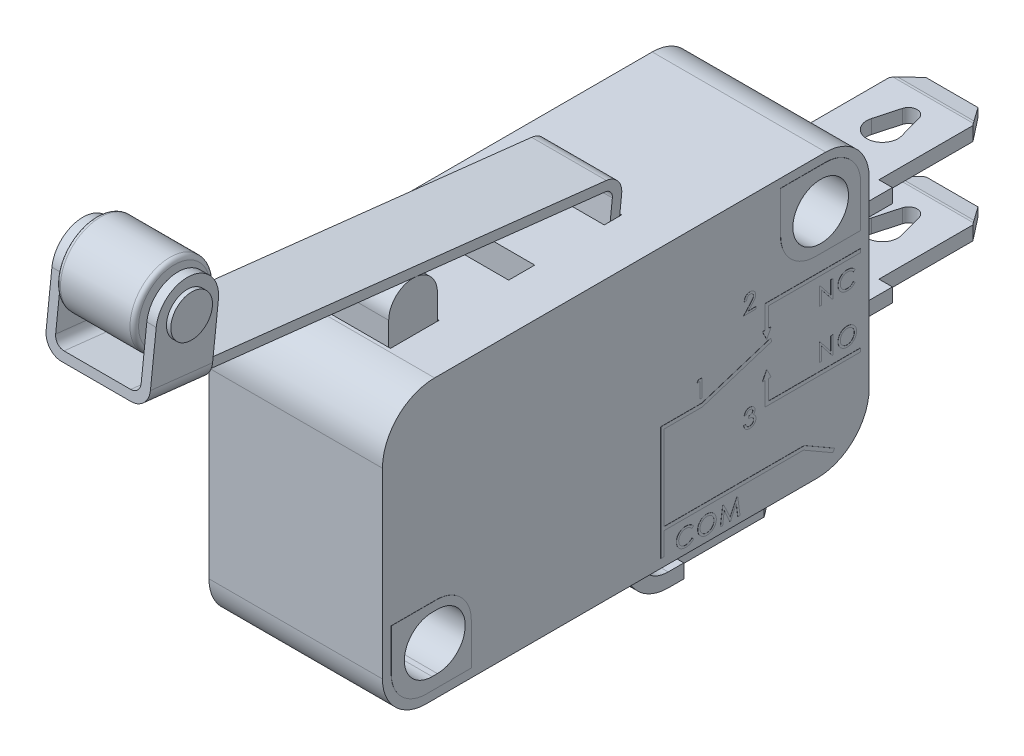
SolidWorks part; units mm, degrees
other "Switch Body"
other "Connections"
other "Lever with Wheel"
material "ABS"
ref_plane "Front Plane" through (0, 0, 0) normal (0, 0, 1) x (1, 0, 0)
ref_plane "Top Plane" through (0, 0, 0) normal (0, 1, 0) x (1, 0, 0)
ref_plane "Right Plane" through (0, 0, 0) normal (1, 0, 0) x (0, 0, -1)
sketch "Sketch1" plane through (0, 0, 0) normal (1, 0, 0) x (0, 0, -1)
  line L0 (-14, 0) -> (0, 0) construction
  line L1 (-11, 8) -> (11.5, 8)
  line L2 (-14, 5) -> (-14, -5.5)
  line L3 (-11.5, -8) -> (11, -8)
  line L4 (14, 5.5) -> (14, -5)
  line L5 (0, 0) -> (14, 0) construction
  line L6 (0, 0) -> (0, -8) construction
  line L7 (0, 0) -> (0, 8) construction
  arc A0 (-11, 8) -> (-14, 5) centre (-11, 5) ccw
  arc A1 (11, -8) -> (14, -5) centre (11, -5) ccw
  arc A2 (-14, -5.5) -> (-11.5, -8) centre (-11.5, -5.5) ccw
  arc A3 (11.5, 8) -> (14, 5.5) centre (11.5, 5.5) cw
  dimension "D3" = 3
  dimension "D4" = 2.5
  dimension "D1" = 28
  dimension "D2" = 16
extrude "Body Extrude" add sketch "Sketch1" along normal mid plane 9.98
sketch "Sketch4" plane through (4.99, 0, 0) normal (1, 0, 0) x (0, 0, -1)
  line L0 (-11.15, -5.2) -> (-10.85, -5.2) construction
  line L1 (-11.15, -3.6) -> (-10.85, -3.6)
  line L2 (-11.15, -6.8) -> (-10.85, -6.8)
  line L3 (-11.15, -5.2) -> (-12.75, -5.2) construction
  line L4 (-10.85, -5.2) -> (-9.25, -5.2) construction
  line L5 (11.2, 5.2) -> (11.2, 6.8) construction
  line L6 (11.2, 6.8) -> (11.2, 8) construction
  line L7 (11.5, 8) -> (-11, 8) construction
  line L8 (11.2, 5.2) -> (12.8, 5.2) construction
  line L9 (12.8, 5.2) -> (14, 5.2) construction
  line L10 (14, -5) -> (14, 5.5) construction
  line L11 (11.2, 5.2) -> (11.2, 3.6) construction
  line L13 (-11.5, -8) -> (11, -8) construction
  line L15 (-14, 5) -> (-14, -5.5) construction
  circle A0 centre (11.2, 5.2) radius 1.6
  arc A1 (-11.15, -3.6) -> (-11.15, -6.8) centre (-11.15, -5.2) ccw
  arc A2 (-10.85, -6.8) -> (-10.85, -3.6) centre (-10.85, -5.2) ccw
  point P4 (-11, -5.2)
  dimension "D1" = 3.2
  dimension "D2" = 3.2
  dimension "D3" = 3.5
  dimension "D4" = 1.2
  dimension "D5" = 1.2
  dimension "D6" = 2.8
  dimension "D7" = 2.8
  dimension "D8" = 11.6
  dimension "D9" = 1.2
  dimension "D10" = 3
  dimension "D11" = 2.8
  dimension "D12" = 11.6
extrude "Mount Holes Cut" cut sketch "Sketch4" against normal up to surface (9.98 mm away) up to face at (-4.99, 0, 0)
sketch "Sketch3" plane through (0, 0, 0) normal (1, 0, 0) x (0, 0, -1)
  line L0 (23.75, 2.5) -> (1.75, 2.5)
  line L1 (1.75, 2.5) -> (1.75, -11)
  line L2 (1.75, -11) -> (11.75, -11)
  line L3 (11.75, -11) -> (11.75, -10.2)
  line L4 (11.75, -10.2) -> (2.55, -10.2)
  line L5 (2.55, -10.2) -> (2.55, -3.25)
  line L6 (2.55, -3.25) -> (23.75, -3.25)
  line L7 (23.75, -3.25) -> (23.75, -2.45)
  line L8 (23.75, -2.45) -> (2.55, -2.45)
  line L9 (2.55, -2.45) -> (2.55, 1.7)
  line L10 (2.55, 1.7) -> (23.75, 1.7)
  line L11 (23.75, 1.7) -> (23.75, 2.5)
  line L12 (23.75, -2.45) -> (23.75, 1.7) construction
  line L13 (2.55, -2.45) -> (2.55, -3.25) construction
  line L14 (11.75, -11) -> (23.75, -11) construction
  line L15 (23.75, -11) -> (23.75, -3.25) construction
  line L16 (11.75, -10.2) -> (23.75, -10.2) construction
  line L17 (14, -5) -> (14, 5.5) construction
  line L18 (11.5, 8) -> (-11, 8) construction
  dimension "D1" = 0.8
  dimension "D2" = 0.8
  dimension "D3" = 10
  dimension "D4" = 12
  dimension "D5" = 5.75
  dimension "D6" = 9.75
  dimension "D7" = 19
  dimension "D8" = 5.5
extrude "Connection Extrude" add sketch "Sketch3" along normal mid plane 6.35 separate body
sketch "Sketch6" plane through (0, 0, -14) normal (0, 0, -1) x (-1, 0, 0)
  line L4 (3.175, 1.7) -> (3.175, 2.5)
  line L5 (3.175, 2.5) -> (-3.175, 2.5)
  line L6 (-3.175, 2.5) -> (-3.175, 1.7)
  line L7 (-3.175, 1.7) -> (3.175, 1.7)
  line L8 (3.175, 1.7) -> (3.175, 2.5)
  line L9 (3.175, 2.5) -> (-3.175, 2.5)
  line L10 (-3.175, 2.5) -> (-3.175, 1.7)
  line L11 (-3.175, 1.7) -> (3.175, 1.7)
  line L12 (3.175, -3.25) -> (3.175, -2.45)
  line L13 (3.175, -2.45) -> (-3.175, -2.45)
  line L14 (-3.175, -2.45) -> (-3.175, -3.25)
  line L15 (-3.175, -3.25) -> (3.175, -3.25)
  line L16 (3.175, -3.25) -> (3.175, -2.45)
  line L17 (3.175, -2.45) -> (-3.175, -2.45)
  line L18 (-3.175, -2.45) -> (-3.175, -3.25)
  line L19 (-3.175, -3.25) -> (3.175, -3.25)
  dimension "D1" = 0
  dimension "D2" = 0
extrude "Connection Cut-1" cut sketch "Sketch6" against normal blind 0.5
sketch "Sketch7" plane through (0, -8, 0) normal (0, -1, 0) x (1, 0, 0)
  line L0 (3.175, -1.75) -> (-3.175, -1.75) construction
  line L1 (-3.175, -1.75) -> (3.175, -1.75)
  line L2 (-3.175, -1.75) -> (-3.175, -2.55)
  line L3 (-3.175, -2.55) -> (3.175, -2.55)
  line L4 (3.175, -1.75) -> (3.175, -2.55)
  line L5 (3.175, -1.75) -> (3.175, -11.75) construction
  line L6 (-3.175, -1.75) -> (-3.175, -11.75) construction
  dimension "D1" = 0.8
extrude "Connection Cut-2" cut sketch "Sketch7" against normal blind 0.5
fillet "Connection Fillet-1" radius 2.5 1 edges at (0, -11, -1.75)
fillet "Connection Fillet-2" radius 1.7 1 edges at (0, -10.2, -2.55)
sketch "Sketch5" plane through (3.175, 0, 0) normal (1, 0, 0) x (0, 0, -1)
  line L0 (23.75, 2.1) -> (22.75, 2.1) construction
  line L1 (23.75, 1.7) -> (23.75, 2.5) construction
  line L2 (23.75, -2.85) -> (22.75, -2.85) construction
  line L3 (23.75, -3.25) -> (23.75, -2.45) construction
  line L4 (11.75, -10.6) -> (10.75, -10.6) construction
  line L5 (11.75, -11) -> (11.75, -10.2) construction
  line L6 (10.75, -11) -> (10.75, -10.2) construction
  line L7 (11.75, -10.2) -> (4.25, -10.2) construction
  line L8 (22.75, -2.45) -> (22.75, -3.25) construction
  line L9 (23.75, -2.45) -> (2.55, -2.45) construction
  line L10 (22.75, 2.5) -> (22.75, 1.7) construction
  line L11 (23.75, 2.5) -> (1.75, 2.5) construction
  line L12 (11.75, -10.35) -> (11.75, -10.85) construction
  line L13 (23.75, 2.35) -> (23.75, 1.85) construction
  line L14 (23.75, -2.6) -> (23.75, -3.1) construction
  line L15 (10.75, -10.2) -> (11.75, -10.2)
  line L16 (11.75, -10.2) -> (11.75, -10.35)
  line L17 (11.75, -10.35) -> (10.75, -10.2)
  line L18 (10.75, -11) -> (11.75, -11)
  line L19 (11.75, -11) -> (11.75, -10.85)
  line L20 (11.75, -10.85) -> (10.75, -11)
  line L21 (22.75, 2.5) -> (23.75, 2.5)
  line L22 (23.75, 2.5) -> (23.75, 2.35)
  line L23 (23.75, 2.35) -> (22.75, 2.5)
  line L24 (22.75, 1.7) -> (23.75, 1.7)
  line L25 (23.75, 1.7) -> (23.75, 1.85)
  line L26 (23.75, 1.85) -> (22.75, 1.7)
  line L27 (22.75, -2.45) -> (23.75, -2.45)
  line L28 (23.75, -2.45) -> (23.75, -2.6)
  line L29 (23.75, -2.6) -> (22.75, -2.45)
  line L30 (22.75, -3.25) -> (23.75, -3.25)
  line L31 (23.75, -3.25) -> (23.75, -3.1)
  line L32 (23.75, -3.1) -> (22.75, -3.25)
  dimension "D1" = 0.5
  dimension "D2" = 1
extrude "Connection Cut-3" cut sketch "Sketch5" against normal up to surface (6.35 mm away) up to face at (-3.175, -4.5193, -9.9879)
fillet "Connection Fillet-3" radius 1 6 edges at (0, 2.5, -22.75) (0, 1.7, -22.75) (0, -3.25, -22.75) (0, -2.45, -22.75) (0, -10.2, -10.75) (0, -11, -10.75)
sketch "Sketch8" plane through (0, -11, 0) normal (0, -1, 0) x (1, 0, 0)
  line L0 (0, 0) -> (0, -5.15) construction
  line L1 (0, -5.15) -> (0, -8.5) construction
  line L2 (0, -8.5) -> (0, -11.75) construction
  line L3 (-3.175, -11.75) -> (3.175, -11.75) construction
  line L4 (2.4, -5.15) -> (-2.4, -5.15) construction
  line L5 (1.5, -11.75) -> (-1.5, -11.75) construction
  line L6 (-2.4, -5.15) -> (-3.175, -5.15)
  line L7 (-3.175, -4.25) -> (-3.175, -10.6754) construction
  line L8 (-3.175, -5.15) -> (-3.175, -11.75)
  line L9 (-3.175, -10.8238) -> (-3.175, -11.75) construction
  line L10 (2.4, -5.15) -> (3.175, -5.15)
  line L11 (3.175, -4.25) -> (3.175, -10.6754) construction
  line L12 (3.175, -5.15) -> (3.175, -11.75)
  line L13 (-2.4, -5.15) -> (-2.4, -10.55)
  line L14 (-2.4, -10.55) -> (-1.5, -11.75)
  line L15 (2.4, -5.15) -> (2.4, -10.55)
  line L16 (2.4, -10.55) -> (1.5, -11.75)
  line L17 (-2.4, -10.55) -> (-3.175, -10.55) construction
  line L18 (2.4, -10.55) -> (3.175, -10.55) construction
  line L19 (-3.175, -11.75) -> (-1.5, -11.75)
  line L20 (1.5, -11.75) -> (3.175, -11.75)
  circle A0 centre (0, -8.5) radius 0.75
  dimension "D1" = 3
  dimension "D6" = 1.5
  dimension "D2" = 4.8
  dimension "D3" = 1.2
  dimension "D4" = 6.6
  dimension "D5" = 3.25
extrude "Connection Cut-4" cut sketch "Sketch8" against normal up to surface (0.8 mm away) up to face at (0, -10.2, -7.4627)
sketch "Sketch9" plane through (0, 8, 0) normal (0, 1, 0) x (1, 0, 0)
  line L0 (0, -14) -> (0, -10.8) construction
  line L1 (4.99, -14) -> (-4.99, -14) construction
  line L2 (0, -10.8) -> (0, -8) construction
  line L3 (-2.25, -8) -> (2.25, -8)
  line L4 (-2.25, -8) -> (-2.25, -10.8)
  line L5 (-2.25, -10.8) -> (2.25, -10.8)
  line L6 (2.25, -8) -> (2.25, -10.8)
  line L7 (0, -8) -> (0, -4) construction
  line L8 (0, -4) -> (0, -2.5) construction
  line L9 (-2.25, -2.5) -> (2.25, -2.5)
  line L10 (-2.25, -2.5) -> (-2.25, -4)
  line L11 (-2.25, -4) -> (2.25, -4)
  line L12 (2.25, -2.5) -> (2.25, -4)
  line L13 (0, -2.5) -> (0, 2) construction
  line L15 (-2.25, 2.5) -> (2.25, 2.5)
  line L16 (-2.25, 2.5) -> (-2.25, 1.5)
  line L17 (-2.25, 1.5) -> (2.25, 1.5)
  line L18 (2.25, 2.5) -> (2.25, 1.5)
  line L19 (-2.25, 2.5) -> (2.25, 1.5) construction
  line L20 (-2.25, 1.5) -> (2.25, 2.5) construction
  dimension "D1" = 2.8
  dimension "D2" = 4.5
  dimension "D3" = 6
  dimension "D4" = 10
  dimension "D5" = 1.5
  dimension "D6" = 16
  dimension "D7" = 1
extrude "Button Cut-1" cut sketch "Sketch9" against normal blind 4
sketch "Sketch10" plane through (0, 2.5, 0) normal (0, 1, 0) x (1, 0, 0)
  line L0 (0, 0) -> (0, 17.15) construction
  line L1 (0, 17.15) -> (0, 23.75) construction
  line L2 (-3.175, 23.75) -> (3.175, 23.75) construction
  line L3 (-2.4, 17.15) -> (2.4, 17.15) construction
  line L4 (-1.5, 23.75) -> (1.5, 23.75) construction
  line L5 (2.4, 17.15) -> (3.175, 17.15)
  line L6 (3.175, 22.6754) -> (3.175, 1.75) construction
  line L7 (3.175, 17.15) -> (3.175, 23.75)
  line L8 (3.175, 23.75) -> (1.5, 23.75)
  line L9 (1.5, 23.75) -> (2.4, 22.55)
  line L10 (2.4, 22.55) -> (2.4, 17.15)
  line L11 (-1.5, 23.75) -> (-2.4, 22.55)
  line L12 (-2.4, 22.55) -> (-2.4, 17.15)
  line L13 (-2.4, 17.15) -> (-3.175, 17.15)
  line L14 (-3.175, 22.6754) -> (-3.175, 1.75) construction
  line L15 (-3.175, 17.15) -> (-3.175, 23.75)
  line L16 (-3.175, 23.75) -> (-1.5, 23.75)
  line L17 (-0.4819, 21.3833) -> (-0.8674, 19.99)
  line L18 (0.4819, 21.3833) -> (0.8674, 19.99)
  arc A0 (-0.8674, 19.99) -> (0.8674, 19.99) centre (0, 19.75) ccw
  arc A1 (0.4819, 21.3833) -> (-0.4819, 21.3833) centre (0, 21.25) ccw
  dimension "D5" = 1
  dimension "D6" = 1.8
  dimension "D1" = 3
  dimension "D2" = 4.8
  dimension "D3" = 6.6
  dimension "D4" = 1.2
  dimension "D7" = 1.5
  dimension "D8" = 4
extrude "Connection Cut-5" cut sketch "Sketch10" against normal up to surface (5.75 mm away) up to face at (0, -3.25, -12.6127)
sketch "Sketch21" plane through (4.99, 0, 0) normal (1, 0, 0) x (0, 0, -1)
  line L0 (11.5, 8) -> (-11, 8) construction
  line L1 (8.9, 7.5) -> (11.5, 7.5)
  line L2 (8.9, 7.5) -> (8.9, 5.1)
  line L3 (10.9, 3.1) -> (13.5, 3.1)
  line L4 (13.5, 5.5) -> (13.5, 3.1)
  line L5 (-10.9, -3.1) -> (-13.5, -3.1)
  line L6 (-8.9, -5.1) -> (-8.9, -7.5)
  line L7 (-8.9, -7.5) -> (-11.5, -7.5)
  line L8 (-13.5, -3.1) -> (-13.5, -5.5)
  line L9 (14, -5) -> (14, 5.5) construction
  line L10 (-11.5, -8) -> (11, -8) construction
  line L11 (-14, 5) -> (-14, -5.5) construction
  line L12 (-11.15, -6.8) -> (-10.85, -6.8) construction
  line L13 (-10.85, -3.6) -> (-11.15, -3.6) construction
  line L14 (-11.15, -6.8) -> (-10.85, -6.8)
  line L15 (-10.85, -3.6) -> (-11.15, -3.6)
  arc A0 (-10.9, -3.1) -> (-8.9, -5.1) centre (-10.9, -5.1) cw
  arc A1 (8.9, 5.1) -> (10.9, 3.1) centre (10.9, 5.1) ccw
  arc A2 (11.5, 7.5) -> (13.5, 5.5) centre (11.5, 5.5) cw
  arc A3 (-11.5, -7.5) -> (-13.5, -5.5) centre (-11.5, -5.5) cw
  arc A4 (-10.85, -6.8) -> (-10.85, -3.6) centre (-10.85, -5.2) ccw construction
  arc A5 (-11.15, -3.6) -> (-11.15, -6.8) centre (-11.15, -5.2) ccw construction
  arc A6 (-10.85, -6.8) -> (-10.85, -3.6) centre (-10.85, -5.2) ccw
  arc A7 (-11.15, -3.6) -> (-11.15, -6.8) centre (-11.15, -5.2) ccw
  circle A8 centre (11.2, 5.2) radius 1.6 construction
  circle A9 centre (11.2, 5.2) radius 1.6
  dimension "D9" = 2
  dimension "D1" = 4.6
  dimension "D2" = 4.6
  dimension "D3" = 4.4
  dimension "D4" = 4.4
  dimension "D5" = 0.5
  dimension "D6" = 0.5
  dimension "D7" = 0.5
  dimension "D8" = 0.5
extrude "Mount Extension" add sketch "Sketch21" along normal blind 0.01
mirror "Mirror Mount Extension" about plane through (0, 0, 0) normal (1, 0, 0) of "Mount Extension"
sketch "Sketch22" plane through (4.99, 0, 0) normal (1, 0, 0) x (0, 0, -1)
  line L0 (23.75, 2.1) -> (14, 2.1) construction
  line L1 (23.75, 1.85) -> (23.75, 2.35) construction
  line L2 (14, -5) -> (14, 5.5) construction
  line L3 (14, 2.1) -> (13.5, 2.1) construction
  line L4 (23.75, -2.85) -> (14, -2.85) construction
  line L5 (23.75, -3.1) -> (23.75, -2.6) construction
  line L6 (14, -2.85) -> (13.5, -2.85) construction
  line L7 (13.5, 2.2) -> (13.5, 2)
  line L8 (13.5, -2.75) -> (13.5, -2.95)
  line L9 (13.5, 2.2) -> (8, 2.2)
  line L10 (13.5, -2.95) -> (8, -2.95)
  line L11 (8, 2.2) -> (8, 0.875)
  line L12 (8, -2.95) -> (8, -1.625)
  line L13 (13.5, 2) -> (8.2, 2)
  line L14 (8.2, 2) -> (8.2, 0.875)
  line L15 (8, 0.875) -> (8.2, 0.875) construction
  line L16 (13.5, -2.75) -> (8.2, -2.75)
  line L17 (8.2, -2.75) -> (8.2, -1.625)
  line L18 (8.2, -1.625) -> (8, -1.625) construction
  line L19 (8.2, 0.875) -> (8.35, 0.875)
  line L20 (8, 0.875) -> (7.85, 0.875)
  line L21 (8.1, 0.875) -> (8.1, 0.375) construction
  line L22 (7.85, 0.875) -> (8.1, 0.375)
  line L23 (8.1, 0.375) -> (8.35, 0.875)
  line L24 (8.2, -1.625) -> (8.35, -1.625)
  line L25 (8, -1.625) -> (7.85, -1.625)
  line L26 (8.1, -1.625) -> (8.1, -1.125) construction
  line L27 (7.85, -1.625) -> (8.1, -1.125)
  line L28 (8.1, -1.125) -> (8.35, -1.625)
  line L29 (-11.5, -8) -> (11, -8) construction
  line L30 (4.5, -1) -> (8.35, 0.225) construction
  line L31 (8.35, 0.225) -> (8.35, 0.875) construction
  line L32 (8.3197, 0.3203) -> (8.3803, 0.1297)
  line L33 (8.3197, 0.3203) -> (4.3631, -0.9386)
  line L34 (4.3631, -0.9386) -> (2, -0.9386)
  line L35 (2, -0.9386) -> (2, -7.5)
  line L36 (2, -7.5) -> (2.2, -7.5)
  line L37 (2.2, -7.5) -> (2.2, -6.2)
  line L38 (2.2, -1.1386) -> (4.3942, -1.1386)
  line L39 (4.3942, -1.1386) -> (8.3803, 0.1297)
  line L40 (2.2, -6) -> (10.2679, -6)
  line L41 (10.2679, -6) -> (12, -7)
  line L42 (12, -7) -> (11.9, -7.1732)
  line L43 (11.9, -7.1732) -> (10.2144, -6.2)
  line L44 (10.2144, -6.2) -> (2.2, -6.2)
  line L45 (2.2, -6) -> (2.2, -1.1386)
  line L46 (2.2, -6) -> (2.2, -6.2) construction
  circle A0 centre (4.5, -1) radius 0.15 construction
  dimension "D7" = 7
  dimension "D8" = 0.3
  dimension "D9" = 9.5
  dimension "D1" = 0.5
  dimension "D2" = 0.2
  dimension "D3" = 5.5
  dimension "D4" = 0.5
  dimension "D5" = 0.5
  dimension "D6" = 1.5
  dimension "D10" = 0.2
  dimension "D11" = 0.65
  dimension "D12" = 0.2
  dimension "D13" = 0.5
  dimension "D14" = 0.2
  dimension "D15" = 12
  dimension "D16" = 2
  dimension "D17" = 0.2
  dimension "D18" = 0.2
  dimension "D19" = 2
  dimension "D20" = 150
  dimension "D21" = 10
extrude "Schematic Lines" add sketch "Sketch22" along normal blind 0.01
sketch "Sketch23" plane through (4.99, 0, 0) normal (1, 0, 0) x (0, 0, -1)
  line L0 (8, 2.2) -> (6.25, 2.2) construction
  line L1 (5.1731, -0.6809) -> (3.4231, -0.6809) construction
  line L2 (8, -3.55) -> (6.25, -3.55) construction
  line L3 (2.55, -7.6327) -> (6.8929, -7.6327) construction
  line L4 (2.55, -8.5) -> (2.55, -3.25) construction
  line L5 (13.5, 0.5) -> (11, 0.5) construction
  line L6 (13.5, 0.5) -> (13.5, -2.3) construction
  line L7 (13.5, -2.3) -> (11, -2.3) construction
  line L8 (8, 2.2) -> (8, 0.875) construction
  line L9 (8, 2.2) -> (8, 0.875) construction
  line L10 (14, -5) -> (14, 5.5) construction
  line L11 (8.2, 2) -> (13.5, 2) construction
  line L12 (8.3197, 0.3203) -> (4.3631, -0.9386) construction
  line L13 (8, -3.55) -> (8, -2.95) construction
  text T0 "1" font "Century Gothic" height 1
  text T1 "2" font "Century Gothic" height 1
  text T2 "3" font "Century Gothic" height 1
  text T3 "COM" font "Century Gothic" height 1
  text T4 "NC" font "Century Gothic" height 1
  text T5 "NO" font "Century Gothic" height 1
  point P15 (8, -2.95)
  dimension "D1" = 0.5
  dimension "D2" = 1.5
  dimension "D3" = 2.8
  dimension "D4" = 2.5
  dimension "D5" = 1.75
  dimension "D6" = 0.85
  dimension "D7" = 0.6
extrude "Schematic Text" add sketch "Sketch23" along normal blind 0.01
sketch "Sketch24" plane through (-4.99, 0, 0) normal (-1, 0, 0) x (0, 0, 1)
  line L0 (-14, 2) -> (-4, 2) construction
  line L1 (-14, -5) -> (-14, 5.5) construction
  line L2 (-4, 2) -> (14, 2) construction
  line L3 (14, 5) -> (14, -5.5) construction
  line L4 (-11.5, 8) -> (11, 8) construction
  text T0 "16(5)A  250V~μ\r\n1E4  T125\r\n16A  125V~" font "Century Gothic" height 1.3
  dimension "D1" = 10
  dimension "D2" = 6
extrude "Specs Text" add sketch "Sketch24" along normal blind 0.01
sketch "Sketch11" plane through (0, 0, 0) normal (1, 0, 0) x (0, 0, -1)
  line L0 (2, 8) -> (2, 0) construction
  line L1 (2.5, 8) -> (1.5, 8) construction
  line L2 (2, 0) -> (0, 0) construction
  circle A0 centre (2, 6) radius 0.75
  dimension "D1" = 2
  dimension "D2" = 1.5
extrude "Button Cut-2" cut sketch "Sketch11" against normal mid plane 4.3
sketch "Sketch Set 0.25 or 2.75" plane through (0, 0, 0) normal (1, 0, 0) x (0, 0, -1)
  line L0 (-8, 4) -> (-10.8, 4) construction
  line L2 (-10.8, 6.75) -> (-8, 6.75)
  line L4 (-9.4, 4) -> (-9.4, 6.75) construction
  line L5 (-10.8, 6.75) -> (-10.8, 9.35)
  line L6 (-10.8, 9.35) -> (-8, 9.35) construction
  line L7 (-8, 9.35) -> (-8, 6.75)
  line L8 (-9.4, 6.75) -> (-9.4, 9.35) construction
  line L9 (-9.4, 9.35) -> (-9.4, 10.75) construction
  line L10 (11.5, 8) -> (-11, 8) construction
  arc A0 (-8, 9.35) -> (-10.8, 9.35) centre (-9.4, 9.35) ccw
  dimension "D2" = 4
  dimension "D1" = 2.8
  dimension "D3" = 2.75
extrude "Switch Button ADJUSTABLE" add sketch "Sketch Set 0.25 or 2.75" along normal mid plane 4.3 separate body
sketch "Sketch13" plane through (0, 0, 0) normal (1, 0, 0) x (0, 0, -1)
  line L0 (1.7317, 6.0301) -> (2.2683, 5.9699) construction
  line L1 (1.8096, 6.7254) -> (2.0657, 9.0114)
  line L2 (1.6597, 9.5198) -> (-25.4705, 12.5591)
  line L3 (2.3462, 6.6653) -> (2.6023, 8.9513)
  line L4 (1.7199, 10.0564) -> (-21.8328, 12.695)
  line L5 (-25.4104, 13.0957) -> (-25.0252, 16.5342) construction
  line L6 (-21.8328, 12.695) -> (-21.4476, 16.1334) construction
  line L7 (-25.0252, 16.5342) -> (-21.4476, 16.1334) construction
  line L8 (2, 6) -> (2.334, 8.9814) construction
  line L9 (1.7317, 6.0301) -> (1.8096, 6.7254) construction
  line L10 (2.2683, 5.9699) -> (2.3462, 6.6653) construction
  line L11 (-21.8328, 12.695) -> (-25.4104, 13.0957)
  line L12 (-25.4104, 13.0957) -> (-25.4705, 12.5591)
  line L13 (-23.2364, 16.3338) -> (-23.4925, 14.0481) construction
  line L14 (-23.2364, 16.3338) -> (-23.6216, 12.8953) construction
  line L15 (2.0657, 9.0114) -> (2.6023, 8.9513) construction
  line L16 (-23.2364, 16.3338) -> (-22.9803, 18.6195) construction
  arc A0 (1.8096, 6.7254) -> (2.3462, 6.6653) centre (2, 6) ccw
  arc A2 (-21.4476, 16.1334) -> (-25.0252, 16.5342) centre (-23.2364, 16.3338) ccw construction
  arc A3 (2.6023, 8.9513) -> (1.7199, 10.0564) centre (1.6085, 9.0626) ccw
  arc A4 (2.0657, 9.0114) -> (1.6597, 9.5198) centre (1.6085, 9.0626) ccw
  circle A5 centre (-23.2364, 16.3338) radius 2.3 construction
  arc A6 (-8, 9.35) -> (-10.8, 9.35) centre (-9.4, 9.35) ccw construction
  dimension "D1" = 1.5
  dimension "D5" = 4
  dimension "D6" = 1
  dimension "D7" = 0.46
  dimension "D8" = 28.3
  dimension "D10" = 4.6
  dimension "D2" = 0.54
  dimension "D3" = 0.54
  dimension "D4" = 3.6
  dimension "D9" = 4
  dimension "D11" = 6.3
extrude "Switch Lever Extrude" add sketch "Sketch13" along normal mid plane 4.3 separate body
sketch "Sketch15" plane through (0, 10.122, -1.1339) normal (0, 0.9938, -0.1113) x (1, 0, 0)
  line L0 (0, -26.7104) -> (0, -22.8604) construction
  line L1 (2.15, -26.7104) -> (-2.15, -26.7104) construction
  line L2 (-1.65, -22.8604) -> (1.65, -22.8604) construction
  line L4 (1.65, -22.8604) -> (2.15, -22.8604) construction
  line L5 (2.15, 0.5896) -> (2.15, -26.7104) construction
  line L6 (-1.65, -22.8604) -> (-2.15, -22.8604) construction
  line L7 (-2.15, 0.5896) -> (-2.15, -26.7104) construction
  line L8 (-1.9, -22.6104) -> (-1.9, -23.1104) construction
  line L9 (1.9, -22.6104) -> (1.9, -23.1104) construction
  line L10 (2.15, -22.6104) -> (2.15, -23.1104)
  line L11 (-2.15, -22.6104) -> (-2.15, -23.1104)
  line L12 (1.9, -22.6104) -> (2.15, -22.6104)
  line L13 (1.9, -23.1104) -> (2.15, -23.1104)
  line L14 (-1.9, -22.6104) -> (-2.15, -22.6104)
  line L15 (-1.9, -23.1104) -> (-2.15, -23.1104)
  arc A0 (1.9, -22.6104) -> (1.9, -23.1104) centre (1.9, -22.8604) ccw
  arc A1 (-1.9, -23.1104) -> (-1.9, -22.6104) centre (-1.9, -22.8604) ccw
  point P14 (1.7648, -22.7252)
  dimension "D1" = 3.6
  dimension "D2" = 0.5
extrude "Lever Cut-1" cut sketch "Sketch15" against normal up to surface (0.54 mm away) up to face at (0, 11.0394, 11.9054)
sketch "Sketch16" plane through (0, 2.9737, 26.5444) normal (0, 0.1113, 0.9938) x (1, 0, 0)
  line L0 (2.15, 9.6454) -> (3, 9.6454)
  line L1 (3, 9.6454) -> (3, 15.4454)
  line L2 (-2.15, 9.6454) -> (-3, 9.6454)
  line L3 (-3, 9.6454) -> (-3, 15.4454)
  line L4 (-3, 15.4454) -> (-2.46, 15.4454)
  line L5 (-2.46, 15.4454) -> (-2.46, 10.1854)
  line L6 (3, 15.4454) -> (2.46, 15.4454)
  line L7 (2.46, 15.4454) -> (2.46, 10.1854)
  line L8 (2.46, 10.1854) -> (2.15, 10.1854)
  line L9 (-2.46, 10.1854) -> (-2.15, 10.1854)
  line L10 (-2.15, 10.1854) -> (-2.15, 9.6454)
  line L11 (2.15, 10.1854) -> (2.15, 9.6454)
  point P8 (2.15, 9.2461)
  dimension "D1" = 6
  dimension "D2" = 5.8
extrude "Lever Side Tabs" add sketch "Sketch16" against normal up to surface (3.6 mm away) up to face at (2.025, 12.4266, 21.8629)
fillet "Lever Fillet-1" 2 edges at (2.73, 18.323, 24.8248) (2.73, 17.9223, 21.2472) type full round first side face at (0, 15.5752, 25.1327) second side face at (2.4533, 14.2585, 21.6576) middle face at (2.73, 18.1226, 23.036)
fillet "Lever Fillet-2" 2 edges at (-2.73, 18.323, 24.8248) (-2.73, 17.9223, 21.2472) type full round first side face at (0, 15.128, 25.1828) second side face at (-2.4533, 14.2585, 21.6576) middle face at (-2.73, 18.1226, 23.036)
fillet "Lever Fillet-3" radius 0.54 2 edges at (2.46, 12.8953, 23.6216) (-2.46, 12.8953, 23.6216)
fillet "Lever Fillet-4" radius 1 2 edges at (-3, 12.3587, 23.6817) (3, 12.3587, 23.6817)
sketch "Sketch18" plane through (0, 0, 0) normal (1, 0, 0) x (0, 0, -1)
  line L0 (-25.0252, 16.5342) -> (-21.4476, 16.1334) construction
  circle A0 centre (-23.2364, 16.3338) radius 1.2
  dimension "D1" = 2.4
extrude "Lever Shaft" add sketch "Sketch18" along normal mid plane 6.5
sketch "Sketch19" plane through (0, 0, 0) normal (1, 0, 0) x (0, 0, -1)
  circle A0 centre (-23.2364, 16.3338) radius 2.3 construction
  circle A1 centre (-23.2364, 16.3338) radius 2.3
extrude "Lever Wheel" add sketch "Sketch19" along normal mid plane 4.5
fillet "Lever Wheel Fillet-1" radius 0.25 2 edges at (-2.25, 16.3338, 20.9364) (2.25, 16.3338, 20.9364)
sketch "Sketch25" plane through (0, 0, 0) normal (1, 0, 0) x (0, 0, -1)
  line L0 (-11.5, -8) -> (11, -8) construction
  line L1 (-14, 5) -> (-14, -5.5) construction
  circle A0 centre (-2, 0) radius 3
  point P3 (0, 0)
  point P4 (-4.2134, 0)
  dimension "D1" = 6
  dimension "D2" = 8
  dimension "D3" = 12
extrude "Hollow Cut" cut sketch "Sketch25" against normal mid plane 2
sketch "Sketch26" plane through (0, 0, 0) normal (1, 0, 0) x (0, 0, -1)
  circle A0 centre (-2, 0) radius 2.05
  dimension "D1" = 4.1
extrude "Real-World Weight Adjustment" add sketch "Sketch26" along normal mid plane 2 separate body
